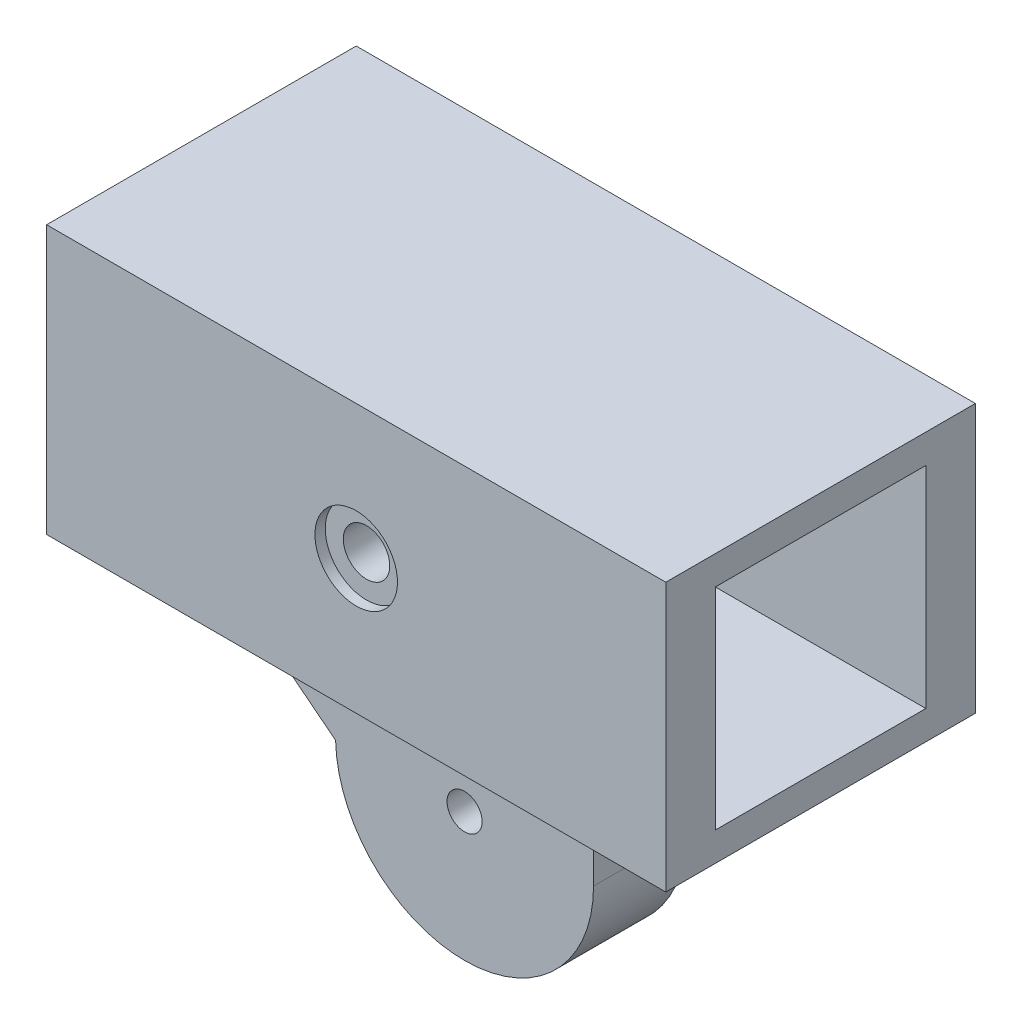
SolidWorks part; units mm, degrees
ref_plane "Plan de face" through (0, 0, 0) normal (0, 0, 1) x (1, 0, 0)
ref_plane "Plan de dessus" through (0, 0, 0) normal (0, 1, 0) x (1, 0, 0)
ref_plane "Plan de droite" through (0, 0, 0) normal (1, 0, 0) x (0, 0, -1)
sketch "Esquisse1" plane through (0, 0, 0) normal (1, 0, 0) x (0, 0, -1)
  line L1 (-15, 26) -> (15, 26)
  line L2 (-15, 26) -> (-15, 0)
  line L3 (-15, 0) -> (15, 0)
  line L4 (15, 26) -> (15, 0)
  dimension "D1" = 30
  dimension "D2" = 26
extrude "Boss.-Extru.1" add sketch "Esquisse1" along normal blind 60
sketch "Esquisse4" plane through (0, 0, 0) normal (0, 0, 1) x (1, 0, 0)
  line L0 (17.5, 0) -> (17.5, -13.5)
  line L1 (60, 0) -> (0, 0) construction
  line L2 (42.5, -13.5) -> (42.5, 0)
  line L3 (42.5, 0) -> (17.5, 0)
  arc A0 (17.5, -13.5) -> (42.5, -13.5) centre (30, -13.5) ccw
  point P6 (30, 0)
  point P8 (30, 0)
  dimension "D1" = 25
extrude "Boss.-Extru.2" add sketch "Esquisse4" along normal mid plane 9
sketch "Esquisse3" plane through (0, 0, 0) normal (-1, 0, 0) x (0, 0, 1)
  line L0 (-15, 26) -> (15, 0) construction
  line L1 (15, 26) -> (-15, 0) construction
  line L2 (-10.2, 23.2) -> (10.2, 23.2)
  line L3 (-10.2, 23.2) -> (-10.2, 2.8)
  line L4 (-10.2, 2.8) -> (10.2, 2.8)
  line L5 (10.2, 23.2) -> (10.2, 2.8)
  line L6 (-10.2, 23.2) -> (10.2, 2.8) construction
  line L7 (-10.2, 2.8) -> (10.2, 23.2) construction
  point P0 (0, 13)
  point P14 (0, 13)
  dimension "D1" = 20.4
  dimension "D2" = 20.4
extrude "Enlèv. mat.-Extru.1" cut sketch "Esquisse3" against normal blind 60
hole_wizard "Dégagement M31" positions "Esquisse5" profile "Esquisse6" hole size "M3" standard "ISO" end condition through all
sketch "Esquisse5" plane through (0, 0, 4.5) normal (0, 0, 1) x (1, 0, 0)
  point P0 (30, -13.5)
sketch "Esquisse6" plane through (30, -13.5, 4.5) normal (1, 0, 0) x (0, -1, 0)
  line L0 (0, 0) -> (0, 19.5)
  line L1 (0, 19.5) -> (1.7, 19.5)
  line L2 (1.7, 19.5) -> (1.7, 0)
  line L5 (1.7, 0) -> (0, 0)
  line L11 (0, -6.35) -> (0, 107.95) construction
  dimension "Diamètre du perçage jusqu'au prochain" = 3.4
  dimension "Profondeur du perçage jusqu'au prochain" = 19.5
sketch "Esquisse7" plane through (0, 0, 0) normal (0, 0, 1) x (1, 0, 0)
  line L0 (0, 0) -> (17.5, -13.7672)
  line L1 (60, 0) -> (0, 0) construction
rib "Nervure3" sketch "Esquisse7" sketch "Esquisse7" thickness 9 extrusion direction parallel to sketch draft on no parameters "D1"=9
hole_wizard "Chambrage pour vis à tête hexagonale M41" positions "Esquisse8" profile "Esquisse9" counterbore size "M4" standard "ISO" end condition up to next
sketch "Esquisse8" plane through (0, 0, 15) normal (0, 0, 1) x (1, 0, 0)
  point P0 (30, 13)
sketch "Esquisse9" plane through (30, 13, 15) normal (1, 0, 0) x (0, -1, 0)
  line L0 (0, 0) -> (0, 4.8)
  line L1 (0, 4.8) -> (2.25, 4.8)
  line L3 (2.25, 4.8) -> (2.25, 1)
  line L4 (2.25, 1) -> (4, 1)
  line L5 (4, 1) -> (4, 0)
  line L7 (4, 0) -> (0, 0)
  line L11 (0, -6.35) -> (0, 107.95) construction
  dimension "Diamètre du perçage jusqu'au prochain" = 4.5
  dimension "Profondeur du perçage jusqu'au prochain" = 4.8
  dimension "Diamètre du chambrage" = 8
  dimension "Profondeur du chambrage" = 1
mirror "Symétrie1" about plane through (0, 0, 0) normal (0, 0, 1) of "Chambrage pour vis à tête hexagonale M41"
